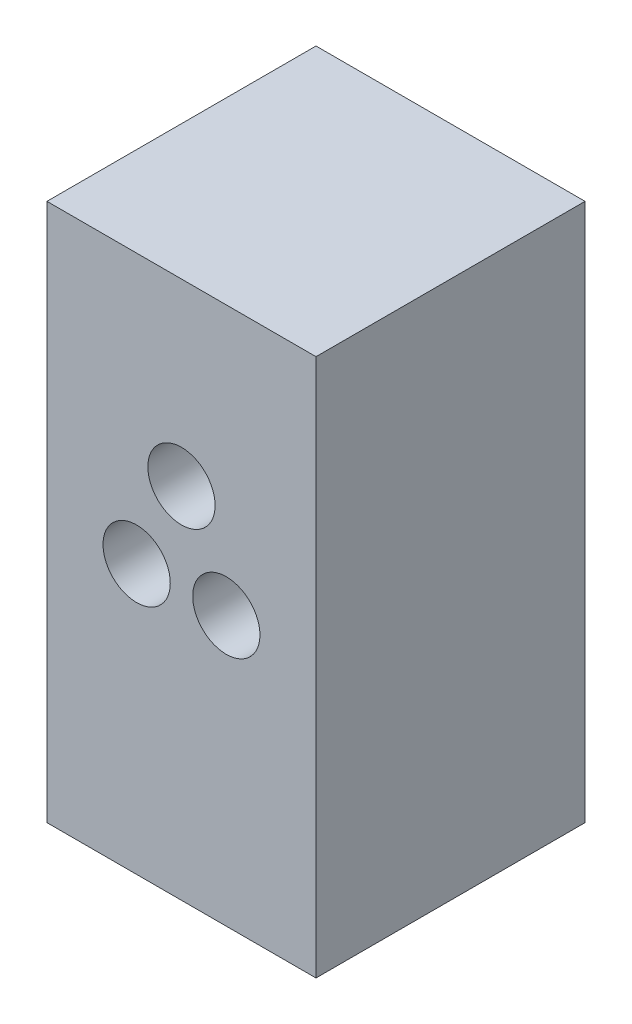
SolidWorks part; units mm, degrees
ref_plane "Front Plane" through (0, 0, 0) normal (0, 0, 1) x (1, 0, 0)
ref_plane "Top Plane" through (0, 0, 0) normal (0, 1, 0) x (1, 0, 0)
ref_plane "Right Plane" through (0, 0, 0) normal (1, 0, 0) x (0, 0, -1)
sketch "Sketch1" plane through (0, 0, 0) normal (0, 0, 1) x (1, 0, 0)
  line L0 (-1.0583, 0) -> (-3.175, 0) construction
  line L1 (-3.175, -6.35) -> (3.175, -6.35)
  line L2 (-3.175, -6.35) -> (-3.175, 6.35)
  line L3 (-3.175, 6.35) -> (3.175, 6.35)
  line L4 (3.175, -6.35) -> (3.175, 6.35)
  line L5 (-3.175, -6.35) -> (3.175, 6.35) construction
  line L6 (-3.175, 6.35) -> (3.175, -6.35) construction
  line L7 (-1.0583, 0) -> (1.0583, 0) construction
  line L8 (1.0583, 0) -> (3.175, 0) construction
  circle A0 centre (0, 2.1167) radius 0.7938
  circle A1 centre (-1.0583, 0) radius 0.7937
  circle A2 centre (1.0583, 0) radius 0.7938
  point P0 (0, 0)
  point P12 (0, 0)
  dimension "D3" = 1.5875
  dimension "D4" = 1.5875
  dimension "D5" = 1.5875
  dimension "D1" = 6.35
  dimension "D2" = 12.7
  dimension "D6" = 2.1167
extrude "Boss-Extrude1" add sketch "Sketch1" along normal blind 6.35 contours L1 L4 L3 L2 A2 A1 A0 | A1 | A0 | A2 region at (0, -0.0561, 0) region at (0, 2.1167, 0) region at (-1.0583, 0, 0) region at (1.0583, 0, 0)
extrude "Cut-Extrude1" cut sketch "Sketch1<3>" against normal blind 1.27 from surface contours A1 | A0 | A2 region at (0, 2.1167, 0) region at (-1.0583, 0, 0) region at (1.0583, 0, 0) starting at face at (0, 0, 6.35)
sketch "Sketch1<3>" plane through (0, 0, 0) normal (0, 0, 1) x (1, 0, 0) same geometry as "Sketch1"
